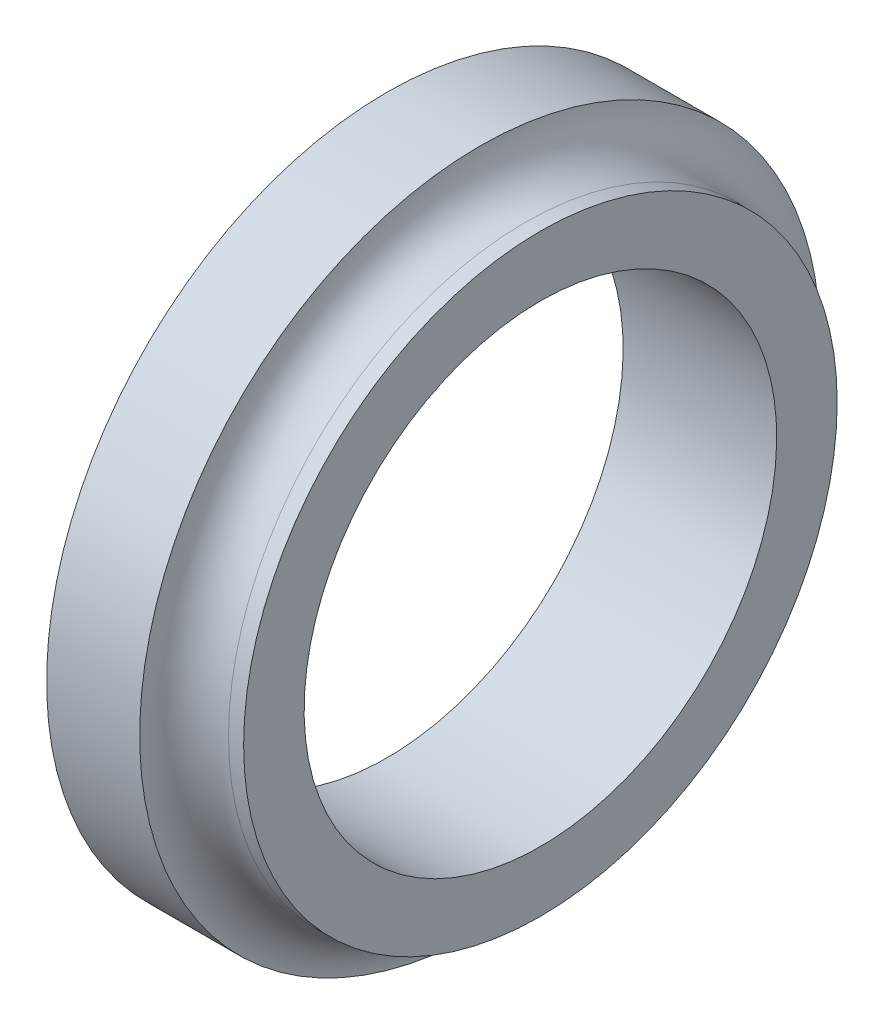
SolidWorks part; units mm, degrees
material "6061-T6 (SS)"
ref_plane "Front Plane" through (0, 0, 0) normal (0, 0, 1) x (1, 0, 0)
ref_plane "Top Plane" through (0, 0, 0) normal (0, 1, 0) x (1, 0, 0)
ref_plane "Right Plane" through (0, 0, 0) normal (1, 0, 0) x (0, 0, -1)
sketch "Sketch1" plane through (0, 0, 0) normal (0, 0, 1) x (1, 0, 0)
  line L0 (-6.0506, 5.715) -> (-6.0506, 3.9687)
  line L1 (-6.0506, 3.9687) -> (-3.4719, 3.9687)
  line L2 (-3.4719, 3.9687) -> (-3.4719, 4.9847)
  line L3 (-3.4719, 4.9847) -> (-3.7259, 4.9847)
  line L4 (-4.4872, 5.715) -> (-6.0506, 5.715)
  line L7 (-3.4719, 6.1516) -> (-3.4719, -6.1516) construction
  line L8 (0, 0) -> (-12.5654, 0) construction
  arc A0 (-3.7259, 4.9847) -> (-4.4872, 5.715) centre (-3.7259, 5.7467) cw
  dimension "D1" = 0.762
  dimension "D2" = 0.254
  dimension "D3" = 11.43
  dimension "D4" = 1.016
revolve "Revolve1" add sketch "Sketch1" angle 360 about L8
